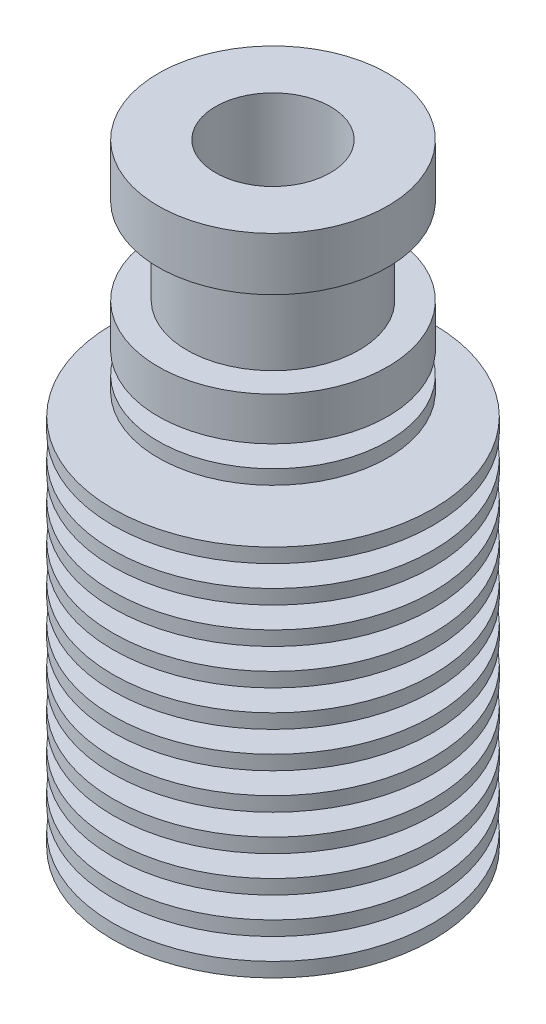
SolidWorks part; units mm, degrees
material "1060 Alloy"
ref_plane "Front Plane" through (0, 0, 0) normal (0, 0, 1) x (1, 0, 0)
ref_plane "Top Plane" through (0, 0, 0) normal (0, 1, 0) x (1, 0, 0)
ref_plane "Right Plane" through (0, 0, 0) normal (1, 0, 0) x (0, 0, -1)
sketch "Sketch1" plane through (0, 0, 0) normal (0, 0, 1) x (1, 0, 0)
  line L0 (11.15, 18.5) -> (5.0829, 18.5)
  line L1 (5.0829, 18.5) -> (5.0829, 20)
  line L2 (5.0829, 20) -> (11.15, 20)
  line L3 (11.15, 20) -> (11.15, 21)
  line L4 (11.15, 21) -> (4.9518, 21)
  line L5 (4.9518, 21) -> (4.9518, 22.5)
  line L6 (4.9518, 22.5) -> (11.15, 22.5)
  line L7 (11.15, 22.5) -> (11.15, 23.5)
  line L8 (11.15, 23.5) -> (4.8208, 23.5)
  line L9 (4.8208, 23.5) -> (4.8208, 25)
  line L10 (4.8208, 25) -> (11.15, 25)
  line L11 (11.15, 25) -> (11.15, 26)
  line L12 (11.15, 26) -> (4.6898, 26)
  line L13 (4.6898, 26) -> (4.6898, 27.5)
  line L14 (4.6898, 27.5) -> (8, 27.5)
  line L15 (8, 27.5) -> (8, 28.5)
  line L16 (8, 28.5) -> (4.6898, 28.5)
  line L17 (4.6898, 28.5) -> (4.6898, 30)
  line L18 (4.6898, 30) -> (8, 30)
  line L19 (8, 30) -> (8, 33)
  line L20 (8, 33) -> (6, 33)
  line L21 (6, 33) -> (6, 39)
  line L22 (6, 39) -> (8, 39)
  line L23 (8, 39) -> (8, 42.7)
  line L24 (8, 42.7) -> (4, 42.7)
  line L25 (4, 42.7) -> (4, 36.6)
  line L26 (4, 36.6) -> (2.1, 34.7)
  line L27 (2.1, 34.7) -> (2.1, 14.7)
  line L28 (2.1, 14.7) -> (3.5, 13.3)
  line L29 (3.5, 13.3) -> (3.5, 0)
  line L30 (3.5, 0) -> (11.15, 0)
  line L31 (11.15, 0) -> (11.15, 1)
  line L32 (11.15, 1) -> (6, 1)
  line L33 (6, 1) -> (6, 2.5)
  line L34 (6, 2.5) -> (11.15, 2.5)
  line L35 (11.15, 2.5) -> (11.15, 3.5)
  line L36 (11.15, 3.5) -> (5.869, 3.5)
  line L37 (5.869, 3.5) -> (5.869, 5)
  line L38 (5.869, 5) -> (11.15, 5)
  line L39 (11.15, 5) -> (11.15, 6)
  line L40 (11.15, 6) -> (5.738, 6)
  line L41 (5.738, 6) -> (5.738, 7.5)
  line L42 (5.738, 7.5) -> (11.15, 7.5)
  line L43 (11.15, 7.5) -> (11.15, 8.5)
  line L44 (11.15, 8.5) -> (5.6069, 8.5)
  line L45 (5.6069, 8.5) -> (5.6069, 10)
  line L46 (5.6069, 10) -> (11.15, 10)
  line L47 (11.15, 10) -> (11.15, 11)
  line L48 (11.15, 11) -> (5.4759, 11)
  line L49 (5.4759, 11) -> (5.4759, 12.5)
  line L50 (5.4759, 12.5) -> (11.15, 12.5)
  line L51 (11.15, 12.5) -> (11.15, 13.5)
  line L52 (11.15, 13.5) -> (5.3449, 13.5)
  line L53 (5.3449, 13.5) -> (5.3449, 15)
  line L54 (5.3449, 15) -> (11.15, 15)
  line L55 (11.15, 15) -> (11.15, 16)
  line L56 (11.15, 16) -> (5.2139, 16)
  line L57 (5.2139, 16) -> (5.2139, 17.5)
  line L58 (5.2139, 17.5) -> (11.15, 17.5)
  line L59 (11.15, 17.5) -> (11.15, 18.5)
  line L60 (0, 42.7) -> (0, 0) construction
revolve "Revolve1" add sketch "Sketch1" angle 360 about L60 reverse direction yes
